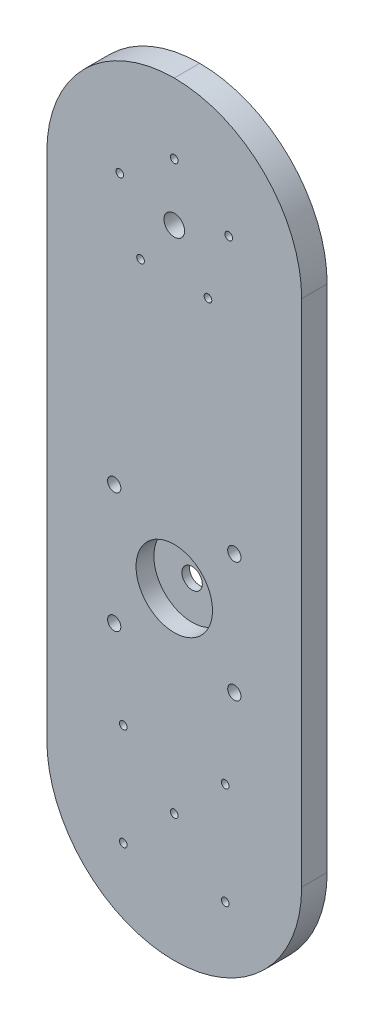
SolidWorks part; units mm, degrees
material "6061 Legierung"
ref_plane "Ebene vorne" through (0, 0, 0) normal (0, 0, 1) x (1, 0, 0)
ref_plane "Ebene oben" through (0, 0, 0) normal (0, 1, 0) x (1, 0, 0)
ref_plane "Ebene rechts" through (0, 0, 0) normal (1, 0, 0) x (0, 0, -1)
sketch "Skizze1" plane through (0, 0, 0) normal (0, 0, 1) x (1, 0, 0)
  line L0 (0, 0) -> (0, 50000) construction
  line L1 (-50, 250) -> (50, 250)
  line L2 (-50, 250) -> (-50, -50)
  line L3 (-50, -50) -> (50, -50)
  line L4 (50, 250) -> (50, -50)
  line L5 (-50, 250) -> (50, -50) construction
  line L6 (-50, -50) -> (50, 250) construction
  point P0 (0, 100)
  point P8 (0, -50)
  dimension "D1" = 100
  dimension "D2" = 300
  dimension "D3" = 50
extrude "Aufsatz-Linear austragen1" add sketch "Skizze1" along normal blind 10
fillet "Verrundung1" radius 50 4 edges at (50, -50, 5) (-50, -50, 5) (-50, 250, 5) (50, 250, 5)
sketch "RiemenSchema" plane through (0, 0, 10) normal (0, 0, 1) x (1, 0, 0)
  line L0 (-37.0077, 193.2123) -> (-15.0932, 73.7317)
  line L1 (37.0077, 193.2123) -> (15.0932, 73.7317)
  line L3 (-28.5, 48) -> (28.5, 48) construction
  line L4 (-28.5, 48) -> (-28.5, 105) construction
  line L5 (-28.5, 105) -> (28.5, 105) construction
  line L6 (28.5, 48) -> (28.5, 105) construction
  line L7 (-28.5, 48) -> (28.5, 105) construction
  line L8 (-28.5, 105) -> (28.5, 48) construction
  circle A0 centre (0, 0) radius 76.5 construction
  circle A1 centre (0, 200) radius 50 construction
  circle A2 centre (0, 200) radius 37.625
  circle A3 centre (0, 76.5) radius 15.345
  dimension "D1" = 153
  dimension "D2" = 75.25
  dimension "D3" = 30.69
  dimension "D4" = 57
  dimension "D5" = 57
hole_wizard "Ø3.0 (3) Durchmesser Bohrung1" positions "Skizze3" profile "Skizze4" hole size "Ø3.0" standard "ISO" end condition through all
sketch "Skizze3" plane through (0, 0, 10) normal (0, 0, 1) x (1, 0, 0)
  line L1 (-20, -20) -> (20, -20)
  line L2 (-20, -20) -> (-20, 20)
  line L3 (-20, 20) -> (20, 20)
  line L4 (20, -20) -> (20, 20)
  line L5 (-20, -20) -> (20, 20) construction
  line L6 (-20, 20) -> (20, -20) construction
  point P1 (0, 0)
  point P2 (20, 20)
  point P37 (-20, -20)
  point P38 (-20, 20)
  point P39 (20, -20)
  point P51 (121.9963, 109.0985)
  dimension "D1" = 40
  dimension "D2" = 40
sketch "Skizze4" plane through (0, 0, 10) normal (1, 0, 0) x (0, -1, 0)
  line L0 (0, 0) -> (0, 10)
  line L1 (0, 10) -> (1.5, 10)
  line L2 (1.5, 10) -> (1.5, 0)
  line L5 (1.5, 0) -> (0, 0)
  line L11 (0, -6.35) -> (0, 107.95) construction
  dimension "Bohrerdurchmesser" = 3
  dimension "Bohrungstiefe" = 10
hole_wizard "Ø5.2 (5.2) Durchmesser Bohrung2" positions "Skizze9" profile "Skizze8" hole size "Ø5.2" standard "ISO" end condition through all
sketch "Skizze9" plane through (0, 0, 10) normal (0, 0, 1) x (1, 0, 0)
  line L1 (-23.57, 52.93) -> (23.57, 52.93)
  line L2 (-23.57, 52.93) -> (-23.57, 100.07)
  line L3 (-23.57, 100.07) -> (23.57, 100.07)
  line L4 (23.57, 52.93) -> (23.57, 100.07)
  line L5 (-28.5, 48) -> (28.5, 105) construction
  line L6 (-28.5, 105) -> (28.5, 48) construction
  point P1 (-23.57, 52.93)
  point P2 (23.57, 100.07)
  point P295 (-23.57, 100.07)
  point P296 (23.57, 52.93)
  dimension "D1" = 47.14
sketch "Skizze8" plane through (-23.57, 52.93, 10) normal (1, 0, 0) x (0, -1, 0)
  line L0 (0, 0) -> (0, 10)
  line L1 (0, 10) -> (2.6, 10)
  line L2 (2.6, 10) -> (2.6, 0)
  line L5 (2.6, 0) -> (0, 0)
  line L11 (0, -6.35) -> (0, 107.95) construction
  dimension "Bohrerdurchmesser" = 5.2
  dimension "Bohrungstiefe" = 10
sketch "Skizze11" plane through (0, 0, 10) normal (0, 0, 1) x (1, 0, 0)
  circle A0 centre (0, 76.5) radius 15
  dimension "D1" = 30
extrude "Schnitt-Linear austragen1" cut sketch "Skizze11" against normal blind 7
hole_wizard "Ø8.0 (8) Durchmesser Bohrung1" positions "Skizze12" profile "Skizze13" hole size "Ø8.0" standard "ISO" end condition through all
sketch "Skizze12" plane through (0, 0, 10) normal (0, 0, 1) x (1, 0, 0)
  point P0 (0, 76.5)
sketch "Skizze13" plane through (0, 76.5, 10) normal (1, 0, 0) x (0, -1, 0)
  line L0 (0, 0) -> (0, 10)
  line L1 (0, 10) -> (4, 10)
  line L2 (4, 10) -> (4, 0)
  line L5 (4, 0) -> (0, 0)
  line L11 (0, -6.35) -> (0, 107.95) construction
  dimension "Bohrerdurchmesser" = 8
  dimension "Bohrungstiefe" = 10
sketch "Skizze14" plane through (0, 0, 10) normal (0, 0, 1) x (1, 0, 0)
  line L0 (-28.5, 105) -> (28.5, 48) construction
  circle A0 centre (0, 76.5) radius 19.1
  dimension "D1" = 38.2
sketch "Skizze15" plane through (0, 0, 10) normal (0, 0, 1) x (1, 0, 0)
  circle A0 centre (0, 200) radius 4.05
  dimension "D1" = 8.1
extrude "Schnitt-Linear austragen2" cut sketch "Skizze15" against normal through all
hole_wizard "Ø3.0 (3) Durchmesser Bohrung3" positions "Skizze16" profile "Skizze17" hole size "Ø3.0" standard "ISO" end condition through all
sketch "Skizze16" plane through (0, 0, 10) normal (0, 0, 1) x (1, 0, 0)
  circle A0 centre (0, 200) radius 22.5 construction
  point P4 (0, 222.5)
  dimension "D1" = 45
sketch "Skizze17" plane through (0, 222.5, 10) normal (1, 0, 0) x (0, -1, 0)
  line L0 (0, 0) -> (0, 10)
  line L1 (0, 10) -> (1.5, 10)
  line L2 (1.5, 10) -> (1.5, 0)
  line L5 (1.5, 0) -> (0, 0)
  line L11 (0, -6.35) -> (0, 107.95) construction
  dimension "Bohrerdurchmesser" = 3
  dimension "Bohrungstiefe" = 10
pattern_circular "Kreismuster1" count 5 over 360 about axis through (0, 200, 10) along (0, 0, 1) of "Ø3.0 (3) Durchmesser Bohrung3"
